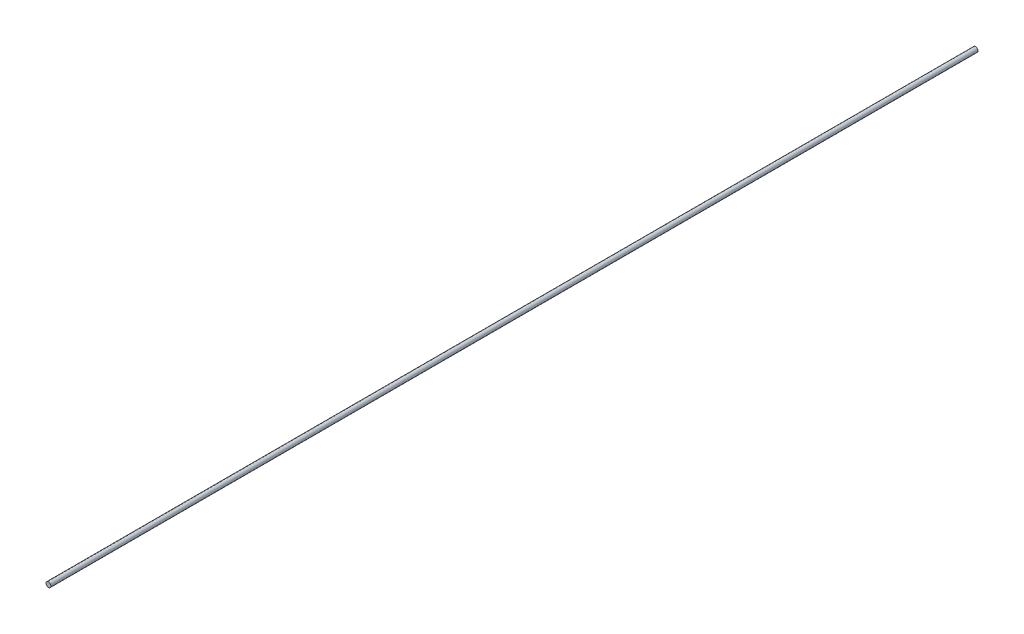
SolidWorks part; units mm, degrees
ref_plane "Front Plane" through (0, 0, 0) normal (0, 0, 1) x (1, 0, 0)
ref_plane "Top Plane" through (0, 0, 0) normal (0, 1, 0) x (1, 0, 0)
ref_plane "Right Plane" through (0, 0, 0) normal (1, 0, 0) x (0, 0, -1)
sketch "Sketch1" plane through (0, 0, 0) normal (0, 0, 1) x (1, 0, 0)
  circle A0 centre (0, 0) radius 2
  dimension "D1" = 4
extrude "Boss-Extrude1" add sketch "Sketch1" along normal blind 761
